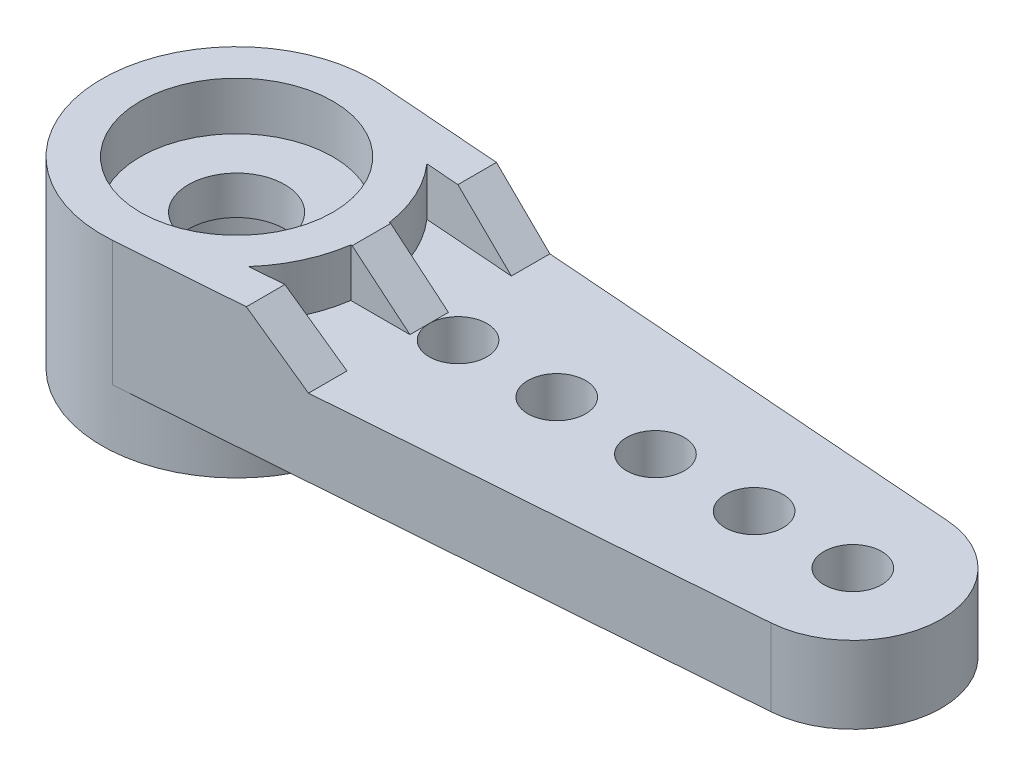
SolidWorks part; units mm, degrees
ref_plane "前视基准面" through (0, 0, 0) normal (0, 0, 1) x (1, 0, 0)
ref_plane "上视基准面" through (0, 0, 0) normal (0, 1, 0) x (1, 0, 0)
ref_plane "右视基准面" through (0, 0, 0) normal (1, 0, 0) x (0, 0, -1)
other "Configuration Table"
sketch "草图1" plane through (0, 0, 0) normal (0, 1, 0) x (1, 0, 0)
  line L0 (0.2625, 3.4901) -> (16.1725, 2.2935)
  line L1 (0.2625, -3.4901) -> (16.1725, -2.2935)
  arc A0 (0.2625, 3.4901) -> (0.2625, -3.4901) centre (0, 0) ccw
  arc A1 (16.1725, -2.2935) -> (16.1725, 2.2935) centre (16, 0) ccw
  point P9 (1.4695, -3.1766)
  point P10 (0, 0)
  dimension "D1" = 3.5
  dimension "D2" = 2.3
  dimension "D3" = 16
extrude "凸台-拉伸1" add sketch "草图1" along normal blind 2
sketch "草图2" plane through (0, 0, 0) normal (0, -1, 0) x (1, 0, 0)
  circle A0 centre (0, 0) radius 3.5
  arc A1 (0.2625, 3.4901) -> (0.2625, -3.4901) centre (0, 0) ccw construction
extrude "凸台-拉伸2" add sketch "草图2" along normal blind 1.5
sketch "草图3" plane through (0, -1.5, 0) normal (0, -1, 0) x (1, 0, 0)
  circle A0 centre (0, 0) radius 2.6
  dimension "D1" = 5.2
extrude "切除-拉伸1" cut sketch "草图3" against normal blind 2.5
sketch "草图4" plane through (0, 2, 0) normal (0, 1, 0) x (1, 0, 0)
  circle A0 centre (0, 0) radius 3.5
  arc A1 (0.2625, 3.4901) -> (0.2625, -3.4901) centre (0, 0) ccw construction
extrude "凸台-拉伸3" add sketch "草图4" along normal blind 1.25
sketch "草图5" plane through (0, 3.25, 0) normal (0, 1, 0) x (1, 0, 0)
  circle A0 centre (0, 0) radius 2.5
  dimension "D1" = 5
extrude "切除-拉伸2" cut sketch "草图5" against normal blind 1.25
sketch "草图6" plane through (0, 2, 0) normal (0, 1, 0) x (1, 0, 0)
  circle A0 centre (0, 0) radius 1.25
  dimension "D1" = 2.5
extrude "切除-拉伸3" cut sketch "草图6" against normal through all
ref_plane "基准面1" through (5, 0, 0) normal (1, 0, 0) x (0, 0, -1)
sketch "草图8" plane through (5, 0, 0) normal (1, 0, 0) x (0, 0, -1)
  line L1 (-0.5, 3.25) -> (0.5, 3.25)
  line L2 (-0.5, 3.25) -> (-0.5, 2)
  line L3 (-0.5, 2) -> (0.5, 2)
  line L4 (0.5, 3.25) -> (0.5, 2)
  line L5 (3.4901, 2) -> (-3.4901, 2) construction
  line L6 (2.2935, 2) -> (-2.2935, 2) construction
  line L8 (2.5, 3.25) -> (-2.5, 3.25) construction
  point P8 (0, 2)
  dimension "D1" = 1
extrude "凸台-拉伸4" add sketch "草图8" against normal up to surface (1.5359 mm away) up to face at (1.8813, 1, 0)
sketch "草图9" plane through (0, 2, 0) normal (0, 1, 0) x (1, 0, 0)
  line L1 (0.2625, 3.4901) -> (5, 3.1338)
  line L4 (5, 3.1338) -> (5, 2.1338)
  line L5 (16.1725, 2.2935) -> (0.2625, 3.4901) construction
  line L6 (2.6274, 2.3123) -> (5, 2.1338)
  line L7 (0, 0) -> (16, 0) construction
  line L8 (0.2625, -3.4901) -> (5, -3.1338)
  line L9 (5, -3.1338) -> (5, -2.1338)
  line L10 (2.6274, -2.3123) -> (5, -2.1338)
  line L11 (5, -0.5) -> (5, 0.5) construction
  arc A0 (3.4641, 0.5) -> (3.4641, -0.5) centre (0, 0) ccw construction
  arc A1 (3.4641, 0.5) -> (0.2625, 3.4901) centre (0, 0) ccw construction
  arc A2 (0.2625, 3.4901) -> (2.6274, 2.3123) centre (0, 0) cw
  arc A3 (16.1725, -2.2935) -> (16.1725, 2.2935) centre (16, 0) ccw construction
  arc A4 (0.2625, -3.4901) -> (2.6274, -2.3123) centre (0, 0) ccw
  dimension "D1" = 1
extrude "凸台-拉伸5" add sketch "草图9" along normal up to surface (1.25 mm away) up to face at (0, 3.25, 2.5)
chamfer "倒角2" distance 1.5 distance2 1.25 3 edges at (5, 3.25, 2.6338) (5, 3.25, -2.6338) (5, 3.25, 0) first distance on face at (0, 3.25, 2.5)
sketch "草图10" plane through (0, 2, 0) normal (0, 1, 0) x (1, 0, 0)
  line L0 (0, 0) -> (16, 0) construction
  line L1 (5, -0.5) -> (5, 0.5) construction
  arc A0 (16.1725, -2.2935) -> (16.1725, 2.2935) centre (16, 0) ccw construction
  circle A1 centre (5.75, 0) radius 0.75
  circle A2 centre (8.3125, 0) radius 0.75
  circle A3 centre (10.875, 0) radius 0.75
  circle A4 centre (13.4375, 0) radius 0.75
  circle A5 centre (16, 0) radius 0.75
  point P10 (15.9383, 0)
  dimension "D1" = 1.5
  dimension "D2" = 5
extrude "切除-拉伸4" cut sketch "草图10" against normal through all
